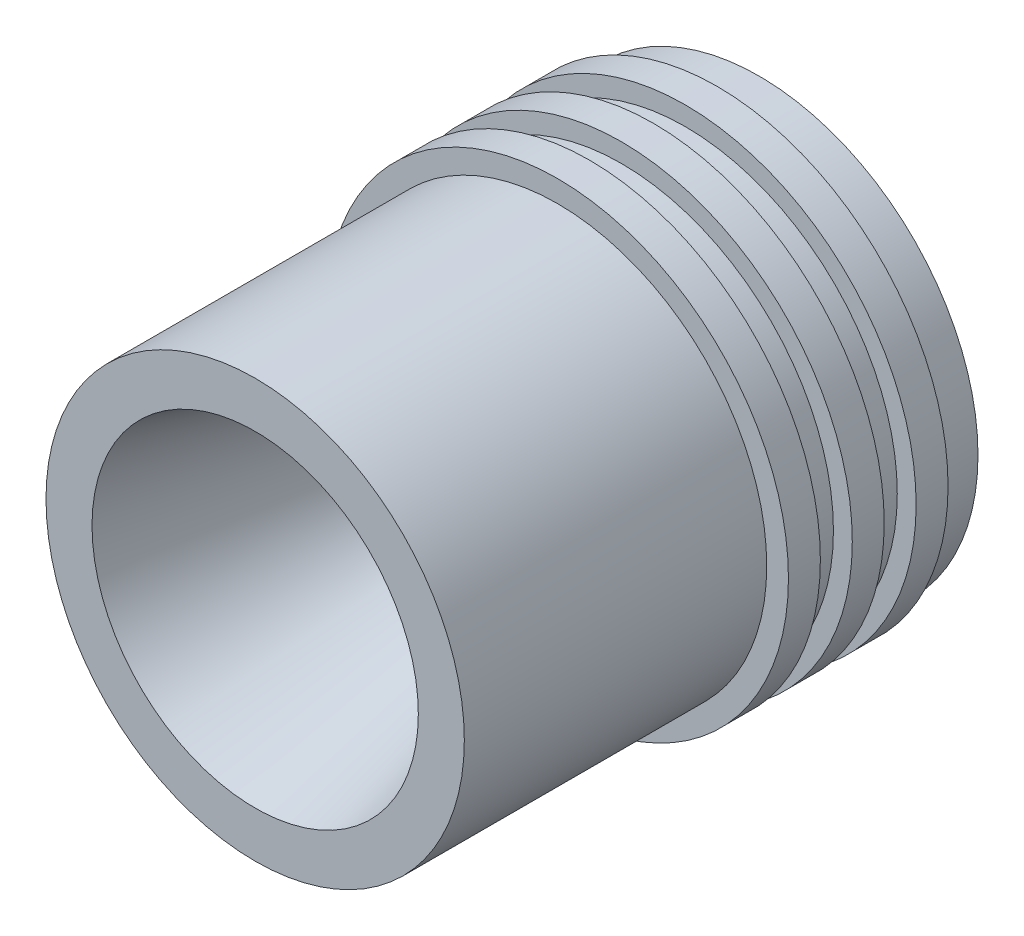
SolidWorks part; units mm, degrees
material "LE Phenolic"
ref_plane "Front Plane" through (0, 0, 0) normal (0, 0, 1) x (1, 0, 0)
ref_plane "Top Plane" through (0, 0, 0) normal (0, 1, 0) x (1, 0, 0)
ref_plane "Right Plane" through (0, 0, 0) normal (1, 0, 0) x (0, 0, -1)
sketch "Sketch1" plane through (0, 0, 0) normal (0, 1, 0) x (1, 0, 0)
  line L0 (69.8119, 139.7) -> (69.8119, 91.44)
  line L1 (63.246, 91.44) -> (63.246, 0)
  line L2 (63.246, 91.44) -> (69.8119, 91.44)
  line L8 (66.167, 139.7) -> (66.167, 152.4)
  line L10 (69.8119, 139.7) -> (66.167, 139.7)
  line L12 (66.167, 152.4) -> (59.817, 152.4)
  line L13 (59.817, 152.4) -> (17.145, 127.7633)
  line L14 (17.145, 127.7633) -> (17.145, 120.1433)
  line L15 (17.145, 120.1433) -> (49.3373, 0)
  line L16 (49.3373, 0) -> (63.246, 0)
  dimension "D1" = 69.8119
  dimension "D2" = 63.246
  dimension "D3" = 48.26
  dimension "D4" = 12.7
  dimension "D5" = 66.167
  dimension "D6" = 15
  dimension "D7" = 60
  dimension "D8" = 152.4
  dimension "D9" = 6.35
  dimension "D10" = 7.62
  dimension "D11" = 17.145
ref_axis "Axis1" through (0, 0, 8.1452) along (0, 0, -1)
revolve "Revolve1" add sketch "Sketch1" angle 360 about axis through (0, 0, 8.1452) along (0, 0, -1)
sketch "Sketch2" plane through (0, 0, 0) normal (0, 1, 0) x (1, 0, 0)
  line L0 (0, -8.1452) -> (0, 171.0497) construction
  line L1 (64.1096, 130.048) -> (70.4596, 130.048)
  line L2 (64.1096, 130.048) -> (64.1096, 120.396)
  line L3 (64.1096, 120.396) -> (70.4596, 120.396)
  line L4 (70.4596, 130.048) -> (70.4596, 120.396)
  line L5 (64.1096, 110.744) -> (70.4596, 110.744)
  line L6 (64.1096, 110.744) -> (64.1096, 101.092)
  line L7 (64.1096, 101.092) -> (70.4596, 101.092)
  line L8 (70.4596, 110.744) -> (70.4596, 101.092)
  line L9 (-69.8119, 91.44) -> (69.8119, 91.44) construction
  dimension "D1" = 9.652
  dimension "D2" = 9.652
  dimension "D3" = 64.1096
  dimension "D4" = 9.652
  dimension "D5" = 9.652
  dimension "D6" = 6.35
revolve "Cut-Revolve1" cut sketch "Sketch2" angle 360 about axis through (0, 0, 8.1452) along (0, 0, -1)
sketch "Sketch3" plane through (0, 0, 0) normal (0, 1, 0) x (1, 0, 0)
  line L0 (17.145, 120.1433) -> (49.3373, 0) construction
  line L1 (17.145, 127.7633) -> (17.145, 120.1433) construction
  line L2 (59.817, 152.4) -> (17.145, 127.7633) construction
  line L3 (17.145, 120.1433) -> (49.3373, 0) construction
  line L4 (17.145, 127.7633) -> (17.145, 120.1433) construction
  line L5 (59.817, 152.4) -> (17.145, 127.7633) construction
  line L6 (50.8, 147.194) -> (50.8, 126.6703)
  line L7 (30.6211, 69.85) -> (17.145, 120.1433)
  line L8 (50.8, 126.6703) -> (40.7811, 69.85)
  line L9 (40.7811, 69.85) -> (30.6211, 69.85)
  line L10 (17.145, 120.1433) -> (17.145, 127.7633)
  line L11 (17.145, 127.7633) -> (50.8, 147.194)
  line L12 (59.817, 152.4) -> (-59.817, 152.4) construction
  dimension "D1" = 10.16
  dimension "D2" = 50.8
  dimension "D3" = 10
  dimension "D4" = 82.55
revolve "Cut-Revolve2" cut sketch "Sketch3" angle 360 about axis through (0, 0, 8.1452) along (0, 0, -1)
